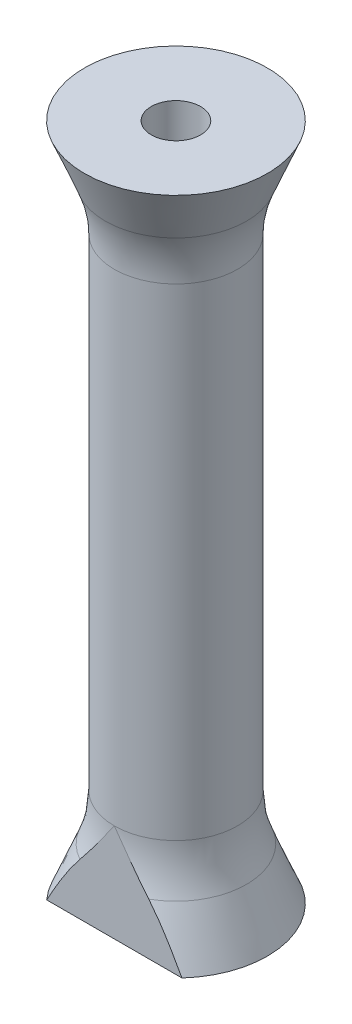
SolidWorks part; units mm, degrees
ref_plane "Front Plane" through (0, 0, 0) normal (0, 0, 1) x (1, 0, 0)
ref_plane "Top Plane" through (0, 0, 0) normal (0, 1, 0) x (1, 0, 0)
ref_plane "Right Plane" through (0, 0, 0) normal (1, 0, 0) x (0, 0, -1)
sketch "Sketch1" plane through (0, 0, 0) normal (0, 1, 0) x (1, 0, 0)
  circle A0 centre (0, 0) radius 6.35
  circle A1 centre (0, 0) radius 2.667
  dimension "D1" = 12.7
  dimension "D2" = 5.334
extrude "Boss-Extrude1" add sketch "Sketch1" along normal blind 69.85
sketch "Sketch2" plane through (0, 0, 0) normal (0, -1, 0) x (-1, 0, 0)
  circle A0 centre (0, 0) radius 9.525
  circle A1 centre (0, 0) radius 2.54
  dimension "D1" = 19.05
extrude "Boss-Extrude2" add sketch "Sketch2" against normal blind 7.62
chamfer "Chamfer1" distance 3.175 angle 68 1 edges at (0, 7.62, -9.525) first distance on face at (0, 7.62, -6.35)
fillet "Fillet1" radius 12.7 1 edges at (0, 7.62, -6.35)
sketch "Sketch3" plane through (0, 69.85, 0) normal (0, 1, 0) x (1, 0, 0)
  circle A0 centre (0, 0) radius 9.525
  circle A1 centre (0, 0) radius 2.54
  dimension "D1" = 19.05
extrude "Boss-Extrude3" add sketch "Sketch3" against normal blind 7.62
chamfer "Chamfer2" distance 3.175 angle 68 1 edges at (0, 62.23, 9.525) first distance on face at (0, 62.23, 6.35)
fillet "Fillet2" radius 12.7 1 edges at (0, 62.23, 6.35)
sketch "Sketch4" plane through (0, 0, 0) normal (0, 0, 1) x (1, 0, 0)
  line L1 (-14.5993, 37.9681) -> (14.5993, 37.9681)
  line L2 (-14.5993, 37.9681) -> (-14.5993, -4.7123)
  line L3 (-14.5993, -4.7123) -> (14.5993, -4.7123)
  line L4 (14.5993, 37.9681) -> (14.5993, -4.7123)
  line L5 (-14.5993, 37.9681) -> (14.5993, -4.7123) construction
  line L6 (-14.5993, -4.7123) -> (14.5993, 37.9681) construction
  point P0 (0, 16.6279)
extrude "Cut-Extrude1" cut sketch "Sketch4" along normal through all from offset 6.35
